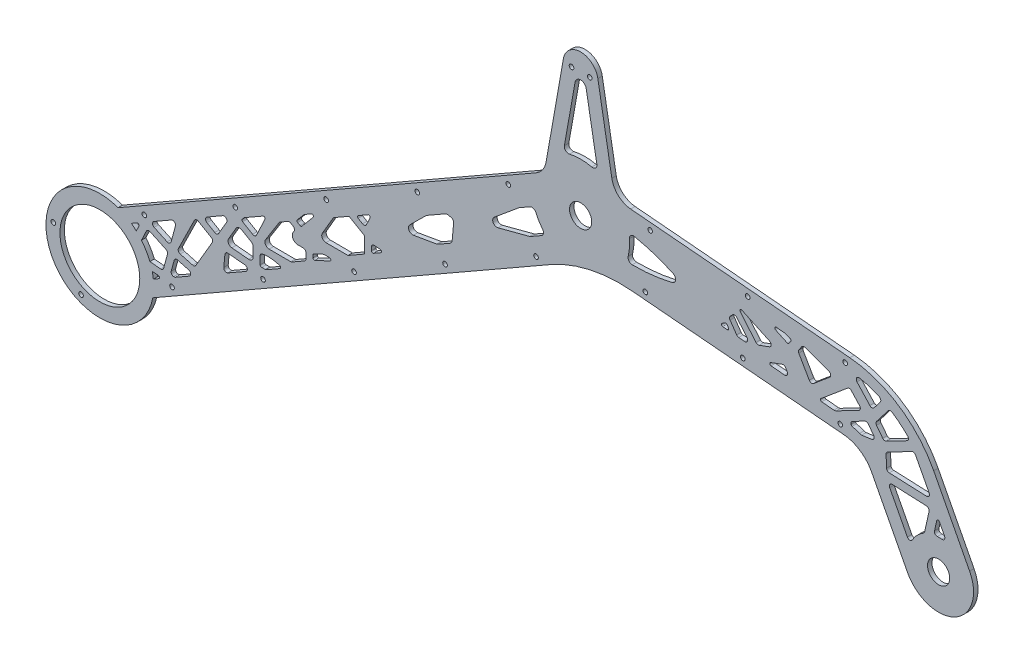
SolidWorks part; units mm, degrees
material "6061-T6 (SS)"
ref_plane "Front Plane" through (0, 0, 0) normal (0, 0, 1) x (1, 0, 0)
ref_plane "Top Plane" through (0, 0, 0) normal (0, 1, 0) x (1, 0, 0)
ref_plane "Right Plane" through (0, 0, 0) normal (1, 0, 0) x (0, 0, -1)
sketch "Reference Sketch" plane through (0, 0, 0) normal (0, 0, 1) x (1, 0, 0)
  line L0 (-343.92, -196.825) -> (0, 0) construction
  line L1 (-243.92, 103.175) -> (356.08, 103.175) construction
  line L2 (-243.92, 103.175) -> (-243.92, 0) construction
  line L3 (-243.92, 0) -> (356.08, 0) construction
  line L4 (356.08, 103.175) -> (356.08, 0) construction
  line L5 (0, 0) -> (256.08, -92.7116) construction
  line L6 (256.08, -92.7116) -> (56.08, -196.825) construction
  line L7 (256.08, -92.7116) -> (456.08, -196.825) construction
  line L8 (-343.92, -196.825) -> (56.08, -196.825) construction
  line L9 (56.08, -196.825) -> (456.08, -196.825) construction
  circle A1 centre (-343.92, -196.825) radius 100 construction
  circle A2 centre (56.08, -196.825) radius 100 construction
  circle A3 centre (456.08, -196.825) radius 100 construction
  circle A4 centre (-343.92, -196.825) radius 16.05 construction
  circle A5 centre (-343.92, -196.825) radius 28.55 construction
  circle A6 centre (-343.92, -196.825) radius 38.55 construction
  circle A7 centre (-343.92, -196.825) radius 33.55 construction
  point P13 (-343.92, -296.825)
  point P14 (556.08, -196.825)
  point P17 (-443.92, -196.825)
  dimension "D3" = 32.1
  dimension "D5" = 200
  dimension "D9" = 57.1
  dimension "D10" = 10
  dimension "D11" = 5
  dimension "D1" = 600
  dimension "D2" = 103.175
  dimension "D4" = 243.92
  dimension "D6" = 125
  dimension "D7" = 400
  dimension "D8" = 1000
sketch "Sketch2" plane through (0, 0, 0) normal (0, 0, 1) x (1, 0, 0)
  line L0 (-379.7168, -188.5069) -> (-32.0065, 10.4873)
  line L1 (-354.8814, -231.9028) -> (-21.5627, -41.1449)
  line L2 (-343.92, -196.825) -> (0, 0) construction
  line L3 (-184.3777, -76.7146) -> (-159.5423, -120.1104) construction
  line L4 (-24.685, 20.9013) -> (-12.3101, 91.0831)
  line L5 (12.3101, 91.0831) -> (22.322, 34.3028)
  line L6 (0, 98.4125) -> (0, 112.7) construction
  line L7 (-5.4848, 79.4125) -> (5.4848, 79.4125) construction
  line L8 (5.4848, 79.4125) -> (10.9697, 88.9125) construction
  line L9 (10.9697, 88.9125) -> (5.4848, 98.4125) construction
  line L10 (5.4848, 98.4125) -> (-5.4848, 98.4125) construction
  line L11 (-5.4848, 98.4125) -> (-10.9697, 88.9125) construction
  line L12 (-10.9697, 88.9125) -> (-5.4848, 79.4125) construction
  line L13 (-243.92, 103.175) -> (356.08, 103.175) construction
  line L14 (0, 88.9125) -> (0, 0) construction
  line L15 (35.7868, 21.9646) -> (192.5861, 8.2464)
  line L16 (252.5753, -31.8371) -> (278.2553, -81.1679)
  line L17 (233.9047, -104.2553) -> (208.2247, -54.9245)
  line L18 (36.8237, -28.3172) -> (188.2284, -41.5633)
  line L19 (0, 0) -> (192.5861, -16.8491) construction
  line L21 (-365.6311, -190.9191) -> (-338.0141, -175.1139) construction
  line L22 (-381.5729, -195.33) -> (-361.7045, -230.0467)
  line L23 (256.08, -92.7116) -> (56.08, -196.825) construction
  line L25 (-243.92, 0) -> (356.08, 0) construction
  circle A0 centre (0, 0) radius 7.9375
  circle A1 centre (-343.92, -196.825) radius 16.05
  arc A3 (-12.3101, 91.0831) -> (12.3101, 91.0831) centre (0, 88.9125) cw
  circle A4 centre (0, 88.9125) radius 6.5 construction
  circle A5 centre (-6.5, 88.9125) radius 1.65
  circle A6 centre (6.5, 88.9125) radius 1.65
  circle A7 centre (0, 88.9125) radius 9.5 construction
  arc A8 (252.5753, -31.8371) -> (192.5861, 8.2464) centre (186.0495, -66.4682) ccw
  circle A9 centre (256.08, -92.7116) radius 7.9375
  arc A10 (278.2553, -81.1679) -> (233.9047, -104.2553) centre (256.08, -92.7116) cw
  arc A11 (-21.5627, -41.1449) -> (36.8237, -28.3172) centre (28.1082, -127.9366) cw
  arc A12 (188.2284, -41.5633) -> (208.2247, -54.9245) centre (186.0495, -66.4682) cw
  arc A13 (22.322, 34.3028) -> (35.7868, 21.9646) centre (37.0941, 36.9075) ccw
  arc A14 (-32.0065, 10.4873) -> (-24.685, 20.9013) centre (-39.4572, 23.506) ccw
  circle A17 centre (-343.92, -196.825) radius 22.5 construction
  circle A18 centre (-365.6311, -190.9191) radius 1.65
  circle A19 centre (-338.0141, -175.1139) radius 1.65
  circle A20 centre (-322.2089, -202.7309) radius 1.65
  circle A21 centre (-349.8259, -218.5361) radius 1.65
  arc A27 (-379.7168, -188.5069) -> (-381.5729, -195.33) centre (-377.2333, -192.8465) ccw
  arc A28 (-361.7045, -230.0467) -> (-354.8814, -231.9028) centre (-357.3649, -227.5632) ccw
  circle A29 centre (-343.92, -196.825) radius 33.55 construction
  circle A32 centre (-343.92, -196.825) radius 38.55 construction
  point P16 (-171.96, -98.4125)
  point P64 (-343.92, -196.825)
  dimension "D1" = 15.875
  dimension "D2" = 32.1
  dimension "D3" = 45
  dimension "D5" = 13
  dimension "D6" = 3.3
  dimension "D7" = 6
  dimension "D12" = 50
  dimension "D14" = 100
  dimension "D16" = 15
  dimension "D17" = 5
  dimension "D18" = 25
  dimension "D19" = 3.3
  dimension "D15" = 4
  dimension "D4" = 50
  dimension "D8" = 19
  dimension "D9" = 14.2875
  dimension "D10" = 9.525
  dimension "D11" = 10
  dimension "D13" = 50
extrude "Base" add sketch "Sketch2" along normal blind 3.175
sketch "Sketch3" plane through (0, 0, 3.175) normal (0, 0, 1) x (1, 0, 0)
  line L0 (-343.92, -196.825) -> (0, 0) construction
  line L5 (0, 0) -> (197.3986, -17.2701) construction
  line L6 (192.5861, 8.2464) -> (35.7868, 21.9646) construction
  line L9 (36.8237, -28.3172) -> (188.2284, -41.5633) construction
  line L10 (-31.8958, -41.2976) -> (0, 0) construction
  line L11 (0, 0) -> (46.2693, -24.1244) construction
  circle A0 centre (-357.3649, -227.5632) radius 1.65
  circle A1 centre (-343.92, -196.825) radius 33.55 construction
  arc A2 (-361.7045, -230.0467) -> (-354.8814, -231.9028) centre (-357.3649, -227.5632) ccw construction
  circle A3 centre (-292.2711, -190.3101) radius 1.65
  circle A4 centre (-227.1773, -153.057) radius 1.65
  circle A5 centre (-162.0835, -115.8038) radius 1.65
  circle A6 centre (-96.9897, -78.5507) radius 1.65
  circle A7 centre (-31.8958, -41.2976) radius 1.65
  circle A8 centre (-312.1394, -155.5934) radius 1.65
  circle A9 centre (-377.2333, -192.8465) radius 1.65
  circle A10 centre (-247.0456, -118.3403) radius 1.65
  circle A11 centre (-181.9518, -81.0871) radius 1.65
  circle A12 centre (-116.858, -43.834) radius 1.65
  circle A13 centre (-51.7642, -6.5809) radius 1.65
  circle A14 centre (46.2693, -24.1244) radius 1.65
  circle A15 centre (116.0029, -30.2253) radius 1.65
  circle A16 centre (185.7366, -36.3262) radius 1.65
  circle A17 centre (189.2228, 3.5215) radius 1.65
  circle A18 centre (119.4892, 9.6224) radius 1.65
  circle A19 centre (49.7555, 15.7234) radius 1.65
  dimension "D1" = 3.3
  dimension "D2" = 6
  dimension "D3" = 5
  dimension "D5" = 3
  dimension "D4" = 75
  dimension "D6" = 70
extrude "Strut Holes" cut sketch "Sketch3" against normal through all
sketch "Sketch6" plane through (0, 0, 3.175) normal (0, 0, 1) x (1, 0, 0)
  line L0 (-315.2692, -197.7109) -> (-301.7593, -189.9792)
  line L1 (-354.8814, -231.9028) -> (-21.5627, -41.1449) construction
  line L2 (-289.845, -183.1607) -> (-279.9388, -177.4914)
  line L3 (-225.0683, -146.089) -> (-215.0659, -140.3647)
  line L4 (-202.4189, -105.5114) -> (-200.6862, -106.5205)
  line L5 (-330.4255, -170.6672) -> (-317.3783, -163.2003)
  line L6 (-32.0065, 10.4873) -> (-379.7168, -188.5069) construction
  line L7 (-315.9769, -164.4942) -> (-323.4022, -180.2613)
  line L8 (-325.3934, -181.4009) -> (-327.8261, -181.1787)
  line L9 (-302.165, -188.1154) -> (-317.5291, -186.7124)
  line L10 (-319.5204, -187.852) -> (-321.9207, -192.9489)
  line L11 (-295.5333, -171.6316) -> (-298.2962, -181.7883)
  line L12 (-300.4079, -183.2551) -> (-315.6625, -181.8621)
  line L13 (-317.2901, -179.0183) -> (-310.6415, -164.9005)
  line L14 (-307.9799, -163.9432) -> (-296.6111, -169.2972)
  line L15 (-280.4073, -173.8257) -> (-288.2923, -171.6808)
  line L16 (-290.7472, -173.0857) -> (-292.8686, -180.8843)
  line L17 (-292.7787, -149.122) -> (-305.2156, -156.2396)
  line L18 (-305.0743, -159.7848) -> (-295.766, -164.1685)
  line L19 (-292.984, -162.8841) -> (-289.8554, -151.3828)
  line L20 (-286.4122, -167.0105) -> (-277.4777, -169.4409)
  line L21 (-275.2245, -168.5176) -> (-263.487, -148.3649)
  line L22 (-264.2087, -145.6301) -> (-273.4911, -140.2238)
  line L23 (-276.2919, -141.0684) -> (-287.6814, -164.1971)
  line L24 (-267.3269, -134.556) -> (-255.9817, -128.0631)
  line L25 (-253.26, -130.8055) -> (-258.9575, -140.5878)
  line L26 (-261.6923, -141.3094) -> (-267.3401, -138.02)
  line L27 (-255.2613, -159.7424) -> (-254.4886, -151.2802)
  line L28 (-252.315, -149.4703) -> (-240.2297, -150.5739)
  line L29 (-292.2711, -190.3101) -> (-299.0066, -188.4038) construction
  line L30 (-252.2762, -161.6601) -> (-239.4181, -154.3014)
  line L31 (-246.5402, -131.1894) -> (-251.7948, -140.2114)
  line L32 (-249.4752, -144.7088) -> (-237.508, -145.8016)
  line L33 (-234.2352, -142.8254) -> (-234.2117, -136.6339)
  line L34 (-235.7018, -134.0302) -> (-242.4379, -130.1069)
  line L35 (-229.2226, -139.4963) -> (-229.2439, -145.1246)
  line L36 (-241.7536, -124.7193) -> (-234.6398, -128.8625)
  line L37 (-231.8238, -127.9864) -> (-225.7969, -115.1887)
  line L38 (-227.1983, -113.8948) -> (-240.4869, -121.4998)
  line L39 (-215.6688, -112.1749) -> (-225.38, -127.5855)
  line L40 (-222.8533, -132.1849) -> (-207.4544, -132.2434)
  line L41 (-206.4534, -131.9792) -> (-197.5057, -126.8584)
  line L42 (-196.4991, -125.1302) -> (-196.4845, -121.2849)
  line L43 (-198.4769, -119.2773) -> (-202.2607, -119.2629)
  line L44 (-205.6297, -113.1304) -> (-205.0269, -112.1739)
  line L45 (-205.7124, -109.3794) -> (-207.4618, -108.3605)
  line L46 (-209.4618, -108.3529) -> (-214.9702, -111.5053)
  line L47 (-223.2993, -137.1832) -> (-189.5978, -137.3112) construction
  line L48 (-199.4194, -106.3021) -> (-191.3609, -96.7721)
  line L49 (-192.6212, -95.2585) -> (-197.479, -98.0386)
  line L50 (-198.0128, -98.4831) -> (-202.6792, -104.0016)
  line L51 (-191.4798, -120.0542) -> (-191.4866, -121.8475)
  line L52 (-190.0674, -122.7592) -> (-179.2455, -117.7628)
  line L54 (-190.899, -119.1501) -> (-184.1308, -116.0253)
  line L55 (-183.2849, -115.8411) -> (-179.6609, -115.8549)
  line L56 (-166.4011, -107.9052) -> (-182.2049, -107.8452)
  line L57 (-184.7858, -103.3353) -> (-176.832, -89.6789)
  line L58 (-176.832, -89.6789) -> (-165.639, -83.2731)
  line L59 (-165.639, -83.2731) -> (-154.6405, -89.6789)
  line L60 (-154.6405, -89.6789) -> (-154.6842, -101.1996)
  line L61 (-154.6842, -101.1996) -> (-166.4011, -107.9052)
  line L62 (-176.832, -89.6789) -> (-166.4011, -107.9052) construction
  line L63 (-149.6667, -96.5998) -> (-149.6576, -94.1811)
  line L64 (-147.4757, -92.197) -> (-143.2847, -92.5797)
  line L65 (-142.8789, -94.4434) -> (-148.17, -97.4715)
  line L66 (-159.1247, -79.5451) -> (-152.014, -75.4756)
  line L67 (-150.6126, -76.7696) -> (-153.1821, -82.2258)
  line L68 (-155.9981, -83.102) -> (-159.1313, -81.2771)
  line L69 (-154.1121, -84.2004) -> (-149.6493, -91.9985) construction
  line L70 (-90.8199, -49.6985) -> (-91.8964, -61.4879)
  line L71 (-93.3939, -63.8188) -> (-101.9943, -68.7409)
  line L72 (-102.9747, -69.0935) -> (-119.6299, -71.9651)
  line L73 (-122.2529, -66.8794) -> (-110.6811, -55.3952)
  line L74 (-110.058, -54.9208) -> (-96.7247, -47.2901)
  line L75 (-94.4471, -46.9991) -> (-92.2866, -47.5868)
  line L76 (-102.4534, -69.0036) -> (-110.4008, -55.117) construction
  line L78 (-28.0968, -26.4494) -> (-35.8254, -30.8725)
  line L79 (-36.5501, -31.1694) -> (-59.134, -37.129)
  line L80 (-61.819, -31.9228) -> (-44.3172, -17.3499)
  line L81 (-43.8877, -17.0516) -> (-36.2746, -12.6946)
  line L82 (-44.1155, -17.182) -> (-36.1682, -31.0687) construction
  line L83 (-11.5997, 37.5245) -> (-3.9861, 80.7029)
  line L84 (3.9861, 80.7029) -> (11.5997, 37.5245)
  line L85 (22.322, 34.3028) -> (12.3101, 91.0831) construction
  line L86 (-12.3101, 91.0831) -> (-24.685, 20.9013) construction
  line L87 (192.5861, 8.2464) -> (35.7868, 21.9646) construction
  line L88 (36.8237, -28.3172) -> (188.2284, -41.5633) construction
  line L89 (-227.1773, -153.057) -> (-233.9128, -151.1507) construction
  line L90 (246.076, -72.9136) -> (249.254, -58.5784)
  line L91 (247.3887, -56.1475) -> (222.9622, -55.081)
  line L92 (221.1009, -58.0026) -> (233.7353, -82.273)
  line L93 (208.2247, -54.9245) -> (233.9047, -104.2553) construction
  line L94 (253.1337, -68.7997) -> (254.752, -61.5)
  line L95 (256.6153, -61.2547) -> (260.3456, -68.4206)
  line L96 (278.2553, -81.1679) -> (252.5753, -31.8371) construction
  line L97 (249.3108, -47.2228) -> (239.5975, -28.5637)
  line L98 (236.9, -27.7132) -> (219.5656, -36.7369)
  line L99 (218.491, -38.5982) -> (218.8608, -47.0688)
  line L100 (220.7717, -48.9796) -> (247.4495, -50.1444)
  line L101 (233.4135, -22.7639) -> (218.6181, -30.4658)
  line L102 (216.1079, -29.9093) -> (211.6718, -24.1281)
  line L103 (211.6718, -21.693) -> (220.0072, -10.8302)
  line L104 (209.6166, -31.3057) -> (205.7463, -26.2618)
  line L105 (203.2361, -25.7053) -> (194.0101, -30.5081)
  line L106 (193.4718, -31.3951) -> (193.4718, -32.4967)
  line L107 (201.069, -35.4569) -> (208.2909, -34.5061)
  line L108 (214.3031, -8.4078) -> (209.9577, -14.0708)
  line L109 (197.6887, -4.156) -> (206.8964, -14.2045)
  line L110 (193.6814, -11.6243) -> (199.5455, -18.0239)
  line L111 (198.9945, -21.1491) -> (182.8075, -29.5754)
  line L112 (181.1608, -29.903) -> (172.4826, -29.1438)
  line L113 (171.927, -27.3815) -> (190.9213, -11.4434)
  line L114 (178.1992, -11.0225) -> (166.5918, -20.7623)
  line L115 (163.5742, -20.2302) -> (156.048, -7.1944)
  line L116 (156.1417, -5.0472) -> (158.1885, -2.1242)
  line L117 (160.5108, -1.3919) -> (177.5977, -7.611)
  line L118 (146.6448, -20.9077) -> (147.747, -22.8167)
  line L119 (145.8406, -25.8091) -> (136.23, -24.9682)
  line L120 (135.9751, -23.0324) -> (144.2287, -20.0283)
  line L121 (134.9743, -13.819) -> (127.6718, -16.4769)
  line L122 (125.4557, -15.8831) -> (114.1985, -2.4673)
  line L123 (115.3872, -0.9182) -> (135.1355, -10.127)
  line L124 (139.4306, -1.096) -> (147.8318, -5.0136)
  line L125 (149.0736, -4.6809) -> (150.4259, -2.7496)
  line L126 (149.9488, -1.2363) -> (146.0985, 0.1651)
  line L127 (145.3339, 0.3346) -> (139.9404, 0.8065)
  line L128 (111.6605, -7.2212) -> (119.0455, -16.0223)
  line L129 (117.3391, -19.3002) -> (113.1162, -18.9308)
  line L130 (111.6522, -18.0855) -> (106.8775, -11.2665)
  line L131 (107.1016, -8.7052) -> (108.7142, -7.0926)
  line L132 (104.7039, -15.1361) -> (105.7554, -16.6377)
  line L133 (104.8491, -18.2075) -> (101.6773, -17.93)
  line L134 (101.2644, -16.0678) -> (103.3847, -14.8436)
  arc A0 (-317.584, -197.4764) -> (-320.5599, -195.9279) centre (-322.2089, -202.7309) ccw
  arc A1 (-291.1568, -183.3993) -> (-291.2348, -183.3872) centre (-292.2711, -190.3101) ccw
  arc A2 (-225.7665, -146.2006) -> (-228.1106, -146.1195) centre (-227.1773, -153.057) ccw
  arc A4 (-322.0747, -194.2209) -> (-322.0953, -194.053) centre (-343.92, -196.825) ccw
  arc A5 (-331.3132, -177.1382) -> (-331.3392, -173.0054) centre (-338.0141, -175.1139) ccw
  arc A6 (-329.0005, -180.6569) -> (-330.6088, -179.309) centre (-343.92, -196.825) ccw
  arc A8 (-227.5555, -137.5318) -> (-215.2363, -138.5515) centre (-223.3943, -162.1831) cw
  arc A9 (-241.9747, -123.1658) -> (-241.1717, -122.1478) centre (-247.0456, -118.3403) ccw
  arc A10 (-32.0383, -14.0906) -> (-27.2511, -21.9631) centre (0, 0) ccw
  arc A11 (-251.7948, -140.2114) -> (-249.4752, -144.7088) centre (-249.2024, -141.7213) ccw
  arc A12 (-225.38, -127.5855) -> (-222.8533, -132.1849) centre (-222.8419, -129.1849) ccw
  arc A13 (-182.2049, -107.8452) -> (-184.7858, -103.3353) centre (-182.1935, -104.8452) cw
  arc A14 (-119.6299, -71.9651) -> (-122.2529, -66.8794) centre (-120.1396, -69.0087) cw
  arc A15 (-59.134, -37.129) -> (-61.819, -31.9228) centre (-59.8994, -34.2283) cw
  arc A16 (-7.9627, 34.0822) -> (7.9627, 34.0822) centre (0, 0) cw
  arc A17 (-3.9861, 80.7029) -> (3.9861, 80.7029) centre (0, 80) cw
  arc A18 (34.8636, 3.0867) -> (34.0029, -8.2948) centre (0, 0) cw
  arc A19 (38.4335, 6.2944) -> (66.0977, -2.7713) centre (15.1723, -111.4295) cw
  arc A20 (66.0977, -2.7713) -> (65.4856, -8.7407) centre (64.749, -5.6491) cw
  arc A21 (36.898, -12.0057) -> (65.4856, -8.7407) centre (37.6733, 107.9918) ccw
  arc A22 (245.141, -74.2025) -> (237.26, -82.3165) centre (256.08, -92.7116) ccw
  arc A23 (258.3595, -71.3328) -> (255.1708, -71.2308) centre (256.08, -92.7116) ccw
  arc A24 (222.6875, -10.3732) -> (233.9189, -19.5905) centre (186.0495, -66.4682) cw
  arc A25 (252.5753, -31.8371) -> (192.5861, 8.2464) centre (186.0495, -66.4682) ccw construction
  arc A26 (194.2312, -33.4673) -> (199.4914, -35.2382) centre (186.0495, -66.4682) cw
  arc A27 (208.2247, -54.9245) -> (188.2284, -41.5633) centre (186.0495, -66.4682) ccw construction
  arc A28 (213.5369, -5.3663) -> (199.5667, -0.8459) centre (186.0495, -66.4682) ccw
  arc A29 (218.8608, -47.0688) -> (220.7717, -48.9796) centre (220.8589, -46.9815) ccw
  arc A30 (239.5975, -28.5637) -> (236.9, -27.7132) centre (237.8235, -29.4872) ccw
  arc A31 (219.5656, -36.7369) -> (218.491, -38.5982) centre (220.4891, -38.5109) ccw
  arc A32 (127.6718, -16.4769) -> (125.4557, -15.8831) centre (126.9878, -14.5975) cw
  arc A33 (-240.4869, -121.4998) -> (-241.1717, -122.1478) centre (-239.4934, -123.2356) ccw
  arc A34 (-234.6398, -128.8625) -> (-231.8238, -127.9864) centre (-233.6332, -127.1343) ccw
  arc A35 (-229.2226, -139.4963) -> (-227.5555, -137.5318) centre (-227.2226, -139.5039) cw
  arc A36 (-315.2692, -197.7109) -> (-317.584, -197.4764) centre (-316.2626, -195.9751) cw
  arc A37 (-322.0747, -194.2209) -> (-320.5599, -195.9279) centre (-320.0887, -193.9842) ccw
  arc A38 (-321.9207, -192.9489) -> (-322.0953, -194.053) centre (-320.1113, -193.801) ccw
  arc A39 (-317.5291, -186.7124) -> (-319.5204, -187.852) centre (-317.711, -188.7042) ccw
  arc A40 (-323.4022, -180.2613) -> (-325.3934, -181.4009) centre (-325.2116, -179.4092) cw
  arc A41 (-327.8261, -181.1787) -> (-329.0005, -180.6569) centre (-327.6442, -179.187) cw
  arc A42 (-331.3132, -177.1382) -> (-330.6088, -179.309) centre (-329.3986, -177.7166) ccw
  arc A43 (-330.4255, -170.6672) -> (-331.3392, -173.0054) centre (-329.4321, -172.403) ccw
  arc A44 (-315.6625, -181.8621) -> (-317.2901, -179.0183) centre (-315.4807, -179.8704) cw
  arc A45 (-298.2962, -181.7883) -> (-300.4079, -183.2551) centre (-300.226, -181.2634) cw
  arc A46 (-289.845, -183.1607) -> (-291.1568, -183.3993) centre (-290.8384, -181.4248) cw
  arc A47 (-292.8686, -180.8843) -> (-291.2348, -183.3872) centre (-290.9387, -181.4092) ccw
  arc A48 (-280.4073, -173.8257) -> (-279.9388, -177.4914) centre (-280.9322, -175.7556) cw
  arc A49 (-288.2923, -171.6808) -> (-290.7472, -173.0857) centre (-288.8173, -173.6107) ccw
  arc A50 (-295.5333, -171.6316) -> (-296.6111, -169.2972) centre (-297.4632, -171.1066) ccw
  arc A51 (-310.6415, -164.9005) -> (-307.9799, -163.9432) centre (-308.8321, -165.7526) cw
  arc A52 (-305.2156, -156.2396) -> (-305.0743, -159.7848) centre (-304.2222, -157.9754) ccw
  arc A53 (-292.7787, -149.122) -> (-289.8554, -151.3828) centre (-291.7853, -150.8578) cw
  arc A54 (-295.766, -164.1685) -> (-292.984, -162.8841) centre (-294.9139, -162.3591) ccw
  arc A55 (-286.4122, -167.0105) -> (-287.6814, -164.1971) centre (-285.8872, -165.0807) cw
  arc A56 (-277.4777, -169.4409) -> (-275.2245, -168.5176) centre (-276.9527, -167.511) ccw
  arc A57 (-263.487, -148.3649) -> (-264.2087, -145.6301) centre (-265.2153, -147.3583) ccw
  arc A58 (-273.4911, -140.2238) -> (-276.2919, -141.0684) centre (-274.4977, -141.952) ccw
  arc A59 (-267.3269, -134.556) -> (-267.3401, -138.02) centre (-266.3335, -136.2918) ccw
  arc A60 (-258.9575, -140.5878) -> (-261.6923, -141.3094) centre (-260.6857, -139.5812) cw
  arc A61 (-254.4886, -151.2802) -> (-252.315, -149.4703) centre (-252.4969, -151.462) cw
  arc A62 (-255.2613, -159.7424) -> (-252.2762, -161.6601) centre (-253.2696, -159.9243) ccw
  arc A63 (-239.4181, -154.3014) -> (-240.2297, -150.5739) centre (-240.4115, -152.5656) ccw
  arc A64 (-255.9817, -128.0631) -> (-253.26, -130.8055) centre (-254.9883, -129.7989) cw
  arc A65 (-207.4544, -132.2434) -> (-206.4534, -131.9792) centre (-207.4468, -130.2434) ccw
  arc A66 (-214.9702, -111.5053) -> (-215.6688, -112.1749) centre (-213.9767, -113.2412) ccw
  arc A67 (-207.4618, -108.3605) -> (-209.4618, -108.3529) centre (-208.4684, -110.0887) ccw
  arc A68 (-205.0269, -112.1739) -> (-205.7124, -109.3794) centre (-206.719, -111.1076) ccw
  arc A69 (-202.2607, -119.2629) -> (-205.6297, -113.1304) centre (-202.2456, -115.263) cw
  arc A70 (-196.4845, -121.2849) -> (-198.4769, -119.2773) centre (-198.4845, -121.2773) ccw
  arc A71 (-197.5057, -126.8584) -> (-196.4991, -125.1302) centre (-198.4991, -125.1226) ccw
  arc A72 (-184.1308, -116.0253) -> (-183.2849, -115.8411) centre (-183.2925, -117.8411) cw
  arc A73 (-197.479, -98.0386) -> (-198.0128, -98.4831) centre (-196.4856, -99.7744) ccw
  arc A74 (-149.6576, -94.1811) -> (-147.4757, -92.197) centre (-147.6576, -94.1887) cw
  arc A75 (-153.1821, -82.2258) -> (-155.9981, -83.102) centre (-154.9915, -81.3737) cw
  arc A76 (-90.8199, -49.6985) -> (-92.2866, -47.5868) centre (-92.8116, -49.5167) ccw
  arc A77 (111.6605, -7.2212) -> (108.7142, -7.0926) centre (110.1284, -8.5068) ccw
  arc A78 (106.8775, -11.2665) -> (107.1016, -8.7052) centre (108.5158, -10.1194) cw
  arc A79 (113.1162, -18.9308) -> (111.6522, -18.0855) centre (113.2905, -16.9384) cw
  arc A80 (119.0455, -16.0223) -> (117.3391, -19.3002) centre (117.5134, -17.3078) cw
  arc A81 (134.9743, -13.819) -> (135.1355, -10.127) centre (134.2903, -11.9396) ccw
  arc A82 (146.6448, -20.9077) -> (144.2287, -20.0283) centre (144.9128, -21.9077) ccw
  arc A83 (147.747, -22.8167) -> (145.8406, -25.8091) centre (146.0149, -23.8167) cw
  arc A84 (156.048, -7.1944) -> (156.1417, -5.0472) centre (157.78, -6.1944) cw
  arc A85 (158.1885, -2.1242) -> (160.5108, -1.3919) centre (159.8268, -3.2713) cw
  arc A86 (178.1992, -11.0225) -> (177.5977, -7.611) centre (176.9136, -9.4904) ccw
  arc A87 (166.5918, -20.7623) -> (163.5742, -20.2302) centre (165.3062, -19.2302) cw
  arc A88 (193.6814, -11.6243) -> (190.9213, -11.4434) centre (192.2068, -12.9755) ccw
  arc A89 (199.5455, -18.0239) -> (198.9945, -21.1491) centre (198.071, -19.375) cw
  arc A90 (209.9577, -14.0708) -> (206.8964, -14.2045) centre (208.371, -12.8533) cw
  arc A91 (213.5369, -5.3663) -> (214.3031, -8.4078) centre (212.7164, -7.1903) cw
  arc A92 (233.9189, -19.5905) -> (233.4135, -22.7639) centre (232.49, -20.9899) cw
  arc A93 (222.6875, -10.3732) -> (220.0072, -10.8302) centre (221.5939, -12.0477) ccw
  arc A94 (211.6718, -24.1281) -> (211.6718, -21.693) centre (213.2585, -22.9105) cw
  arc A95 (218.6181, -30.4658) -> (216.1079, -29.9093) centre (217.6946, -28.6918) cw
  arc A96 (205.7463, -26.2618) -> (203.2361, -25.7053) centre (204.1595, -27.4793) ccw
  arc A97 (209.6166, -31.3057) -> (208.2909, -34.5061) centre (208.0299, -32.5232) cw
  arc A98 (246.076, -72.9136) -> (245.141, -74.2025) centre (244.1234, -72.4807) cw
  arc A99 (249.254, -58.5784) -> (247.3887, -56.1475) centre (247.3014, -58.1456) ccw
  arc A100 (222.9622, -55.081) -> (221.1009, -58.0026) centre (222.8749, -57.0791) ccw
  arc A101 (233.7353, -82.273) -> (237.26, -82.3165) centre (235.5093, -81.3495) ccw
  arc A102 (260.3456, -68.4206) -> (258.3595, -71.3328) centre (258.5716, -69.344) cw
  arc A103 (253.1337, -68.7997) -> (255.1708, -71.2308) centre (255.0863, -69.2326) ccw
  arc A104 (249.3108, -47.2228) -> (247.4495, -50.1444) centre (247.5367, -48.1463) cw
  arc A105 (199.5667, -0.8459) -> (197.6887, -4.156) centre (199.1632, -2.8048) ccw
  arc A106 (-215.2363, -138.5515) -> (-215.0659, -140.3647) centre (-215.5626, -139.4968) cw
  arc A107 (-301.7593, -189.9792) -> (-302.165, -188.1154) centre (-302.256, -189.1113) ccw
  arc A108 (-317.3783, -163.2003) -> (-315.9769, -164.4942) centre (-316.8815, -164.0682) cw
  arc A109 (-225.7969, -115.1887) -> (-227.1983, -113.8948) centre (-226.7016, -114.7627) ccw
  arc A110 (-241.7536, -124.7193) -> (-241.9747, -123.1658) centre (-241.2503, -123.8551) cw
  arc A111 (-225.7665, -146.2006) -> (-225.0683, -146.089) centre (-225.565, -145.2211) ccw
  arc A112 (-229.2439, -145.1246) -> (-228.1106, -146.1195) centre (-228.2439, -145.1284) ccw
  arc A113 (-202.4189, -105.5114) -> (-202.6792, -104.0016) centre (-201.9156, -104.6473) cw
  arc A114 (-200.6862, -106.5205) -> (-199.4194, -106.3021) centre (-200.183, -105.6564) ccw
  arc A115 (-191.4798, -120.0542) -> (-190.899, -119.1501) centre (-190.4798, -120.058) cw
  arc A116 (-191.4866, -121.8475) -> (-190.0674, -122.7592) centre (-190.4866, -121.8513) ccw
  arc A117 (-191.3609, -96.7721) -> (-192.6212, -95.2585) centre (-192.1245, -96.1264) ccw
  arc A118 (-179.2455, -117.7628) -> (-179.6609, -115.8549) centre (-179.6647, -116.8549) ccw
  arc A119 (-152.014, -75.4756) -> (-150.6126, -76.7696) centre (-151.5173, -76.3435) cw
  arc A120 (-159.1247, -79.5451) -> (-159.1313, -81.2771) centre (-158.628, -80.413) ccw
  arc A121 (-149.6667, -96.5998) -> (-148.17, -97.4715) centre (-148.6667, -96.6036) ccw
  arc A122 (-143.2847, -92.5797) -> (-142.8789, -94.4434) centre (-143.3756, -93.5755) cw
  arc A123 (101.6773, -17.93) -> (101.2644, -16.0678) centre (101.7644, -16.9338) cw
  arc A124 (104.7039, -15.1361) -> (103.3847, -14.8436) centre (103.8847, -15.7096) ccw
  arc A125 (105.7554, -16.6377) -> (104.8491, -18.2075) centre (104.9362, -17.2113) cw
  arc A126 (114.1985, -2.4673) -> (115.3872, -0.9182) centre (114.9646, -1.8245) cw
  arc A127 (136.23, -24.9682) -> (135.9751, -23.0324) centre (136.3171, -23.972) cw
  arc A128 (139.4306, -1.096) -> (139.9404, 0.8065) centre (139.8532, -0.1897) cw
  arc A129 (172.4826, -29.1438) -> (171.927, -27.3815) centre (172.5698, -28.1476) cw
  arc A130 (194.0101, -30.5081) -> (193.4718, -31.3951) centre (194.4718, -31.3951) ccw
  arc A131 (193.4718, -32.4967) -> (194.2312, -33.4673) centre (194.4718, -32.4967) ccw
  arc A132 (254.752, -61.5) -> (256.6153, -61.2547) centre (255.7283, -61.7164) cw
  arc A133 (146.0985, 0.1651) -> (145.3339, 0.3346) centre (145.0724, -2.654) ccw
  arc A134 (199.4914, -35.2382) -> (201.069, -35.4569) centre (200.6774, -32.4826) ccw
  arc A135 (182.8075, -29.5754) -> (181.1608, -29.903) centre (181.4223, -26.9144) cw
  arc A136 (-7.9627, 34.0822) -> (-11.5997, 37.5245) centre (-8.6452, 37.0035) cw
  arc A137 (7.9627, 34.0822) -> (11.5997, 37.5245) centre (8.6452, 37.0035) ccw
  arc A138 (34.8636, 3.0867) -> (38.4335, 6.2944) centre (37.8519, 3.3513) cw
  arc A139 (34.0029, -8.2948) -> (36.898, -12.0057) centre (36.9174, -9.0058) ccw
  arc A140 (-35.8254, -30.8725) -> (-36.5501, -31.1694) centre (-37.3155, -28.2687) cw
  arc A141 (-44.3172, -17.3499) -> (-43.8877, -17.0516) centre (-42.3976, -19.6554) cw
  arc A142 (-32.0383, -14.0906) -> (-36.2746, -12.6946) centre (-34.7845, -15.2984) ccw
  arc A143 (-27.2511, -21.9631) -> (-28.0968, -26.4494) centre (-29.5869, -23.8456) cw
  arc A144 (-96.7247, -47.2901) -> (-94.4471, -46.9991) centre (-95.2346, -49.8939) cw
  arc A145 (-91.8964, -61.4879) -> (-93.3939, -63.8188) centre (-94.884, -61.2151) cw
  arc A146 (-110.6811, -55.3952) -> (-110.058, -54.9208) centre (-108.5679, -57.5245) cw
  arc A147 (-101.9943, -68.7409) -> (-102.9747, -69.0935) centre (-103.4845, -66.1371) cw
  arc A148 (-246.5402, -131.1894) -> (-242.4379, -130.1069) centre (-243.9478, -132.6992) cw
  arc A149 (-234.2117, -136.6339) -> (-235.7018, -134.0302) centre (-237.2117, -136.6225) ccw
  arc A150 (-237.508, -145.8016) -> (-234.2352, -142.8254) centre (-237.2352, -142.8141) ccw
  arc A151 (150.4259, -2.7496) -> (149.9488, -1.2363) centre (149.6067, -2.176) ccw
  arc A152 (147.8318, -5.0136) -> (149.0736, -4.6809) centre (148.2544, -4.1073) ccw
  point P98 (-116.858, -43.834)
  point P110 (-254.1648, -144.2806)
  point P113 (-228.2654, -132.1643)
  point P143 (34.9003, -2.6394)
  point P203 (218.9408, -48.8997)
  point P206 (238.674, -26.7897)
  point P211 (126.3559, -16.9559)
  point P214 (-240.9361, -121.7569)
  point P217 (-232.7537, -129.961)
  point P220 (-229.2164, -137.8704)
  point P229 (-318.9237, -186.5851)
  point P232 (-323.9988, -181.5282)
  point P235 (-328.5183, -181.1155)
  point P240 (-331.9839, -171.5591)
  point P247 (-290.5028, -183.5371)
  point P252 (-275.7482, -175.0931)
  point P255 (-290.2222, -171.1558)
  point P262 (-308.5502, -158.1479)
  point P265 (-288.588, -146.7237)
  point P268 (-293.6097, -165.184)
  point P271 (-288.7533, -166.3737)
  point P278 (-275.3444, -139.1443)
  point P281 (-270.3335, -136.2766)
  point P288 (-255.6107, -163.5684)
  point P294 (-249.5035, -124.3556)
  point P297 (-206.9185, -132.2454)
  point P300 (-215.403, -111.753)
  point P303 (-208.4596, -107.7794)
  point P308 (-209.4769, -119.2355)
  point P311 (-196.4769, -119.2849)
  point P314 (-196.5035, -126.2849)
  point P329 (110.2575, -5.5492)
  point P334 (112.1872, -18.8495)
  point P337 (122.1491, -19.721)
  point P340 (139.5116, -12.1676)
  point P345 (149.6679, -26.1439)
  point P350 (159.0687, -0.8671)
  point P353 (180.8529, -8.7958)
  point P356 (164.7659, -22.2944)
  point P363 (208.5067, -15.9618)
  point P366 (215.8118, -6.4415)
  point P369 (235.7568, -21.544)
  point P374 (210.7376, -22.9105)
  point P377 (217.1296, -31.2407)
  point P380 (204.7246, -24.9304)
  point P383 (211.7254, -34.054)
  point P390 (219.5014, -54.9299)
  point P393 (235.6626, -85.9753)
  point P396 (262.2729, -72.1228)
  point P401 (250.9103, -50.2955)
  point P406 (-213.2581, -139.3301)
  point P412 (-314.6256, -161.6249)
  point P415 (-224.4456, -112.3194)
  point P420 (-225.4089, -146.284)
  point P423 (-229.2487, -146.3704)
  point P426 (-203.4487, -104.9116)
  point P431 (-191.4774, -119.4171)
  point P434 (-191.4925, -123.4171)
  point P437 (-187.699, -92.4415)
  point P440 (-175.1502, -115.872)
  point P447 (-149.6733, -98.3319)
  point P450 (-140.1262, -92.8681)
  point P453 (98.5177, -17.6536)
  point P458 (106.9854, -18.3944)
  point P463 (131.7364, -24.5751)
  point P468 (170.0776, -28.9333)
  point P471 (193.4718, -30.7883)
  point P474 (193.4718, -33.2883)
  point P477 (255.3467, -58.8176)
  point P484 (182.0319, -29.9792)
  point P491 (34.2849, 7.0387)
  point P494 (32.91, -11.9136)
  point P505 (-24.8853, -24.6115)
  point P508 (-95.6462, -46.6729)
  point P511 (-92.0384, -63.0431)
  point P524 (-234.2477, -146.0993)
  point P527 (151.1734, -1.682)
  point P530 (148.5923, -5.3682)
  dimension "D1" = 14
  dimension "D2" = 10
  dimension "D3" = 2
  dimension "D5" = 22
  dimension "D6" = 9
  dimension "D12" = 5
  dimension "D19" = 7
  dimension "D31" = 7
  dimension "D40" = 25
  dimension "D44" = 19
  dimension "D62" = 5
  dimension "D92" = 35
  dimension "D96" = 3
  dimension "D97" = 10
  dimension "D100" = 15
  dimension "D104" = 30
  dimension "D105" = 120
  dimension "D107" = 43
  dimension "D116" = 65
  dimension "D117" = 8
  dimension "D127" = 9
  dimension "D128" = 6
  dimension "D171" = 2
  dimension "D172" = 1
  dimension "D173" = 3
  dimension "D174" = 1
  dimension "D175" = 4
  dimension "D7" = 35
  dimension "D8" = 35
  dimension "D9" = 20
  dimension "D10" = 22
  dimension "D11" = 20
  dimension "D13" = 5
  dimension "D14" = 45
  dimension "D15" = 45
  dimension "D16" = 17
  dimension "D17" = 15
  dimension "D18" = 5
  dimension "D20" = 55
  dimension "D21" = 5
  dimension "D22" = 45
  dimension "D23" = 23
  dimension "D24" = 34
  dimension "D25" = 60
  dimension "D26" = 5
  dimension "D27" = 5
  dimension "D28" = 5
  dimension "D29" = 30
  dimension "D30" = 24
  dimension "D32" = 55
  dimension "D33" = 35
  dimension "D34" = 25
  dimension "D35" = 5
  dimension "D36" = 6
  dimension "D37" = 60
  dimension "D38" = 5
  dimension "D39" = 20
  dimension "D41" = 11
  dimension "D42" = 35
  dimension "D43" = 60
  dimension "D45" = 19.5
  dimension "D46" = 5
  dimension "D47" = 5
  dimension "D48" = 30
  dimension "D49" = 5
  dimension "D50" = 14
  dimension "D51" = 13
  dimension "D52" = 8.5
  dimension "D53" = 60
  dimension "D54" = 12
  dimension "D55" = 7
  dimension "D56" = 22
  dimension "D57" = 28
  dimension "D58" = 60
  dimension "D59" = 15
  dimension "D60" = 8
  dimension "D61" = 13
  dimension "D63" = 12
  dimension "D64" = 20
  dimension "D65" = 5
  dimension "D66" = 65
  dimension "D67" = 25
  dimension "2" = 18
  dimension "D68" = 8
  dimension "D69" = 4
  dimension "D70" = 14
  dimension "D71" = 15
  dimension "D72" = 13.5
  dimension "D73" = 60
  dimension "D74" = 60
  dimension "D75" = 8
  dimension "D76" = 5
  dimension "D77" = 35
  dimension "D78" = 0.5076
  dimension "D79" = 5
  dimension "D80" = 11
  dimension "D81" = 35
  dimension "D82" = 16
  dimension "D83" = 18
  dimension "D84" = 55
  dimension "D85" = 45
  dimension "D86" = 20
  dimension "D87" = 15
  dimension "D88" = 12
  dimension "D89" = 17
  dimension "D90" = 16
  dimension "D91" = 18
  dimension "D93" = 15
  dimension "D94" = 10
  dimension "D95" = 13
  dimension "D98" = 10
  dimension "D99" = 80
  dimension "D101" = 16
  dimension "D102" = 22
  dimension "D103" = 22
  dimension "D106" = 7
  dimension "D108" = 10
  dimension "D109" = 40
  dimension "D110" = 10
  dimension "D111" = 6
  dimension "D112" = 60
  dimension "D113" = 35
  dimension "D114" = 15
  dimension "D115" = 6
  dimension "D118" = 26.5
  dimension "D119" = 6
  dimension "D120" = 85
  dimension "D121" = 85
  dimension "D122" = 32
  dimension "D123" = 21
  dimension "D124" = 80
  dimension "D125" = 75
  dimension "D126" = 6
  dimension "D129" = 10.5
  dimension "D130" = 80
  dimension "D131" = 12
  dimension "D132" = 8
  dimension "D133" = 6
  dimension "D134" = 2.5
  dimension "D135" = 100
  dimension "D136" = 11.5
  dimension "D137" = 60
  dimension "D138" = 11
  dimension "D139" = 45
  dimension "D140" = 12
  dimension "D141" = 8.5
  dimension "D142" = 12
  dimension "D143" = 18
  dimension "D144" = 80
  dimension "D145" = 21
  dimension "D146" = 60
  dimension "D147" = 60
  dimension "D148" = 15
  dimension "D149" = 12
  dimension "D150" = 18
  dimension "D151" = 25
  dimension "D152" = 9
  dimension "D153" = 12
  dimension "D154" = 6
  dimension "D155" = 15
  dimension "D156" = 20
  dimension "D157" = 10
  dimension "D158" = 13.5
  dimension "D159" = 4.5
  dimension "D160" = 45
  dimension "D161" = 14
  dimension "D162" = 5
  dimension "D163" = 10
  dimension "D164" = 16
  dimension "D165" = 50
  dimension "D166" = 18.5
  dimension "D167" = 50
  dimension "D168" = 4
  dimension "D169" = 8.5
  dimension "D170" = 35
extrude "Lightening Holes" cut sketch "Sketch6" against normal through all
sketch "Sketch7" plane through (0, 0, 3.175) normal (0, 0, 1) x (1, 0, 0)
  circle A13 centre (-357.3649, -227.5632) radius 1.65 construction
  circle A15 centre (-377.2333, -192.8465) radius 1.65 construction
  circle A16 centre (-343.92, -196.825) radius 38.55 construction
  circle A17 centre (-343.92, -196.825) radius 28.55 construction
  circle A26 centre (-357.3649, -227.5632) radius 1.65
  circle A27 centre (-377.2333, -192.8465) radius 1.65
  circle A28 centre (-343.92, -196.825) radius 38.55
  circle A29 centre (-343.92, -196.825) radius 28.55
extrude "Inner Mod Extrusion" add sketch "Sketch7" against normal up to surface (3.175 mm away) up to face at (-260.7262, -135.4767, 0)
extrude "Inner Mod Cut" cut sketch "Sketch7<2>" against normal through all contours A29 region at (-343.92, -196.825, 3.175)
sketch "Sketch7<2>" plane through (0, 0, 3.175) normal (0, 0, 1) x (1, 0, 0) same geometry as "Sketch7"
